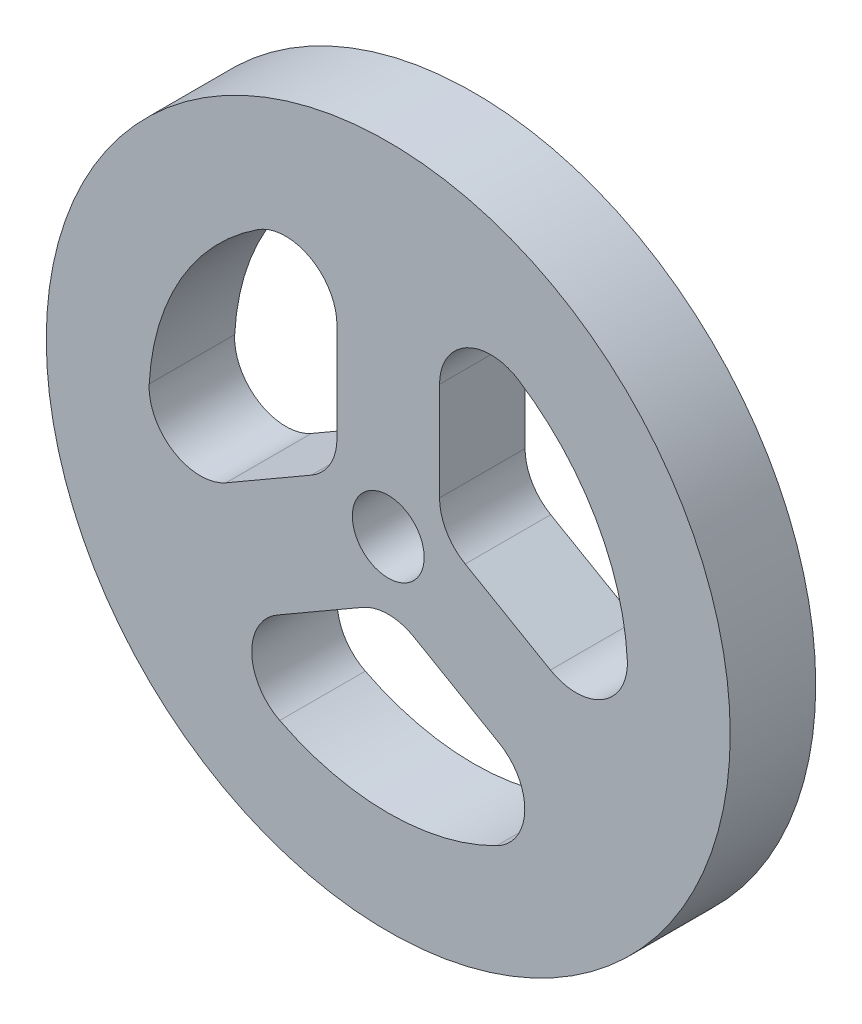
SolidWorks part; units mm, degrees
material "ABS"
ref_plane "Front Plane" through (0, 0, 0) normal (0, 0, 1) x (1, 0, 0)
ref_plane "Top Plane" through (0, 0, 0) normal (0, 1, 0) x (1, 0, 0)
ref_plane "Right Plane" through (0, 0, 0) normal (1, 0, 0) x (0, 0, -1)
sketch "Sketch1" plane through (0, 0, 0) normal (0, 0, 1) x (1, 0, 0)
  line L0 (0, 0) -> (0, 17.78) construction
  line L1 (0, 0) -> (15.3979, -8.89) construction
  line L2 (0, 0) -> (-15.3979, -8.89) construction
  line L3 (-3.81, 2.1997) -> (-17.3029, -5.5904)
  line L4 (0, -4.3994) -> (13.4929, -12.1896)
  line L5 (3.81, 2.1997) -> (3.81, 17.78)
  line L6 (0, -4.3994) -> (-13.4929, -12.1896)
  line L7 (3.81, 2.1997) -> (17.3029, -5.5904)
  line L8 (-3.81, 2.1997) -> (-3.81, 17.78)
  line L9 (1.905, 3.2996) -> (17.3029, -5.5904) construction
  line L10 (3.81, 0) -> (3.81, 17.78) construction
  line L11 (-1.905, 3.2996) -> (-17.3029, -5.5904) construction
  line L12 (-3.81, 0) -> (-3.81, 17.78) construction
  line L13 (-1.905, -3.2996) -> (13.4929, -12.1896) construction
  line L14 (1.905, -3.2996) -> (-13.4929, -12.1896) construction
  circle A0 centre (0, 0) radius 25.4
  circle A1 centre (0, 0) radius 2.667
  arc A3 (-13.1353, -11.9831) -> (13.1353, -11.9831) centre (0, 0) ccw
  arc A4 (16.9453, -5.3839) -> (3.81, 17.367) centre (0, 0) ccw
  arc A5 (-3.81, 17.367) -> (-16.9453, -5.3839) centre (0, 0) ccw
  point P12 (0, 0)
  dimension "D1" = 50.8
  dimension "D2" = 5.334
  dimension "D3" = 7.62
  dimension "D5" = 3.81
  dimension "D6" = 3.81
  dimension "D4" = 3
extrude "Boss-Extrude3" add sketch "Sketch1" along normal blind 6.35 contours A0 A5 L8 L3 A4 L7 L5 A3 L6 L4 A1 region at (-24.6816, 0, 0)
fillet "Fillet1" radius 3.81 9 edges at (0, -4.3994, 3.175) (-13.1353, -11.9831, 3.175) (3.81, 17.367, 3.175) (3.81, 2.1997, 3.175) (-16.9453, -5.3839, 3.175) (-3.81, 2.1997, 3.175) (-3.81, 17.367, 3.175) (13.1353, -11.9831, 3.175) (16.9453, -5.3839, 3.175)
equation "\"rodThick\"= 0.085in"
equation "\"clear\"= 0.003in"
